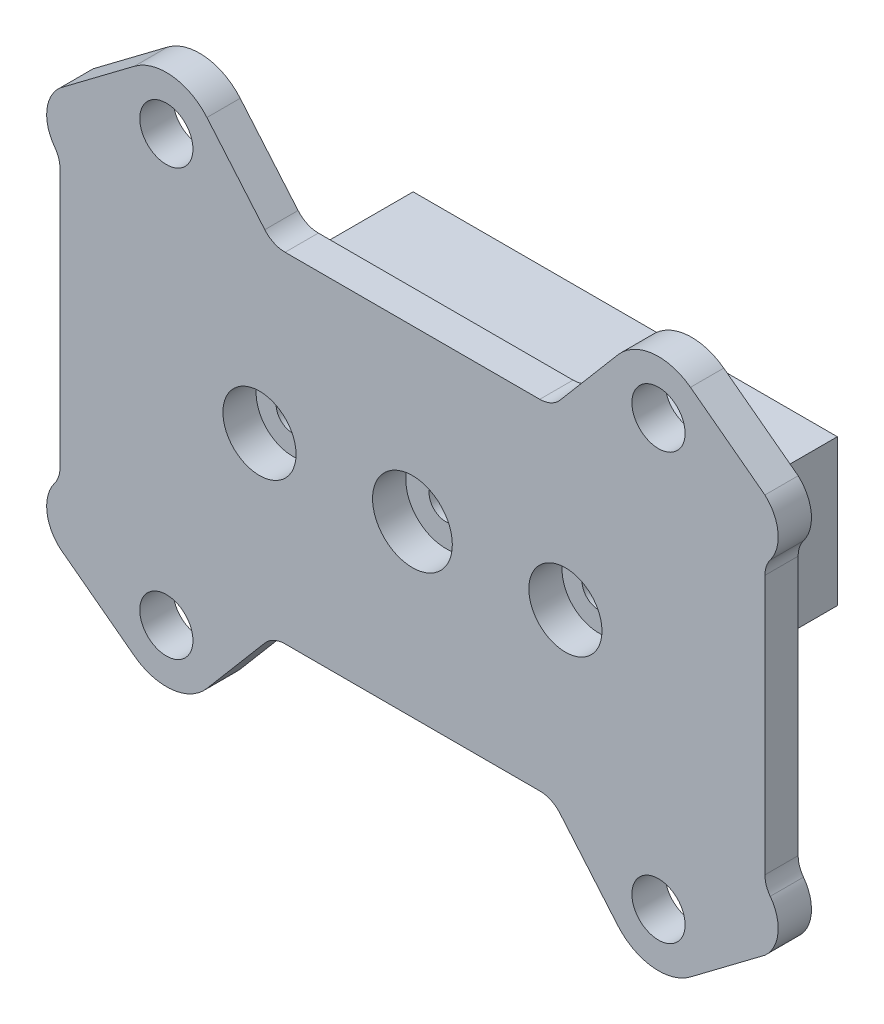
SolidWorks part; units mm, degrees
ref_plane "Front Plane" through (0, 0, 0) normal (0, 0, 1) x (1, 0, 0)
ref_plane "Top Plane" through (0, 0, 0) normal (0, 1, 0) x (1, 0, 0)
ref_plane "Right Plane" through (0, 0, 0) normal (1, 0, 0) x (0, 0, -1)
sketch "Sketch1" plane through (0, 0, 0) normal (0, 0, 1) x (1, 0, 0)
  line L1 (-81.5961, 0) -> (-136.5961, 0) construction
  line L2 (-81.5961, 0) -> (-81.5961, 25.2) construction
  line L3 (-81.5961, 25.2) -> (-136.5961, 25.2) construction
  line L4 (-136.5961, 0) -> (-136.5961, 25.2) construction
  line L5 (-81.5961, 0) -> (-136.5961, 25.2) construction
  line L6 (-81.5961, 25.2) -> (-136.5961, 0) construction
  line L7 (-132.4711, 25.2) -> (-166.0961, 25.2) construction
  line L8 (-146.2488, 0) -> (-142.7398, 0) construction
  line L20 (-97.997, -1.6566) -> (-93.647, -6.7869)
  line L21 (-118.6698, -0.95) -> (-99.5225, -0.95)
  line L22 (-124.5452, -6.7869) -> (-120.1952, -1.6566)
  line L23 (-135.5961, -3.1861) -> (-130.0012, -7.3962)
  line L24 (-135.5961, 21.55) -> (-135.5961, 2.05)
  line L25 (-130.0012, 30.9962) -> (-135.5961, 26.7861)
  line L26 (-120.1952, 25.2566) -> (-124.5452, 30.3869)
  line L27 (-99.5225, 24.55) -> (-118.6698, 24.55)
  line L28 (-93.647, 30.3869) -> (-97.997, 25.2566)
  line L29 (-82.5961, 26.7861) -> (-88.191, 30.9962)
  line L30 (-82.5961, 2.05) -> (-82.5961, 21.55)
  line L31 (-88.191, -7.3962) -> (-82.5961, -3.1861)
  line L32 (-97.997, -1.6566) -> (-93.647, -6.7869)
  line L33 (-118.6698, -0.95) -> (-99.5225, -0.95)
  line L34 (-124.5452, -6.7869) -> (-120.1952, -1.6566)
  line L35 (-135.5961, -3.1861) -> (-130.0012, -7.3962)
  line L36 (-135.5961, 21.55) -> (-135.5961, 2.05)
  line L37 (-130.0012, 30.9962) -> (-135.5961, 26.7861)
  line L38 (-120.1952, 25.2566) -> (-124.5452, 30.3869)
  line L39 (-99.5225, 24.55) -> (-118.6698, 24.55)
  line L40 (-93.647, 30.3869) -> (-97.997, 25.2566)
  line L41 (-82.5961, 26.7861) -> (-88.191, 30.9962)
  line L42 (-82.5961, 2.05) -> (-82.5961, 21.55)
  line L43 (-88.191, -7.3962) -> (-82.5961, -3.1861)
  arc A0 (-82.5961, -3.1861) -> (-82.1961, 0.85) centre (-84.5961, -0.95) ccw construction
  arc A1 (-135.9961, 0.85) -> (-135.5961, -3.1861) centre (-133.5961, -0.95) ccw construction
  arc A18 (-93.647, -6.7869) -> (-88.191, -7.3962) centre (-90.5961, -4.2) ccw
  arc A19 (-97.997, -1.6566) -> (-99.5225, -0.95) centre (-99.5225, -2.95) ccw
  arc A20 (-118.6698, -0.95) -> (-120.1952, -1.6566) centre (-118.6698, -2.95) ccw
  arc A21 (-130.0012, -7.3962) -> (-124.5452, -6.7869) centre (-127.5961, -4.2) ccw
  arc A22 (-135.9961, 0.85) -> (-135.5961, -3.1861) centre (-133.5961, -0.95) ccw
  arc A23 (-135.9961, 0.85) -> (-135.5961, 2.05) centre (-137.5961, 2.05) ccw
  arc A24 (-135.5961, 21.55) -> (-135.9961, 22.75) centre (-137.5961, 21.55) ccw
  arc A25 (-135.5961, 26.7861) -> (-135.9961, 22.75) centre (-133.5961, 24.55) ccw
  arc A26 (-124.5452, 30.3869) -> (-130.0012, 30.9962) centre (-127.5961, 27.8) ccw
  arc A27 (-120.1952, 25.2566) -> (-118.6698, 24.55) centre (-118.6698, 26.55) ccw
  arc A28 (-99.5225, 24.55) -> (-97.997, 25.2566) centre (-99.5225, 26.55) ccw
  arc A29 (-88.191, 30.9962) -> (-93.647, 30.3869) centre (-90.5961, 27.8) ccw
  arc A30 (-82.1961, 22.75) -> (-82.5961, 26.7861) centre (-84.5961, 24.55) ccw
  arc A31 (-82.1961, 22.75) -> (-82.5961, 21.55) centre (-80.5961, 21.55) ccw
  arc A32 (-82.5961, 2.05) -> (-82.1961, 0.85) centre (-80.5961, 2.05) ccw
  arc A33 (-82.5961, -3.1861) -> (-82.1961, 0.85) centre (-84.5961, -0.95) ccw
  arc A34 (-93.647, -6.7869) -> (-88.191, -7.3962) centre (-90.5961, -4.2) ccw
  arc A35 (-97.997, -1.6566) -> (-99.5225, -0.95) centre (-99.5225, -2.95) ccw
  arc A36 (-118.6698, -0.95) -> (-120.1952, -1.6566) centre (-118.6698, -2.95) ccw
  arc A37 (-130.0012, -7.3962) -> (-124.5452, -6.7869) centre (-127.5961, -4.2) ccw
  arc A38 (-135.9961, 0.85) -> (-135.5961, -3.1861) centre (-133.5961, -0.95) ccw
  arc A39 (-135.9961, 0.85) -> (-135.5961, 2.05) centre (-137.5961, 2.05) ccw
  arc A40 (-135.5961, 21.55) -> (-135.9961, 22.75) centre (-137.5961, 21.55) ccw
  arc A41 (-135.5961, 26.7861) -> (-135.9961, 22.75) centre (-133.5961, 24.55) ccw
  arc A42 (-124.5452, 30.3869) -> (-130.0012, 30.9962) centre (-127.5961, 27.8) ccw
  arc A43 (-120.1952, 25.2566) -> (-118.6698, 24.55) centre (-118.6698, 26.55) ccw
  arc A44 (-99.5225, 24.55) -> (-97.997, 25.2566) centre (-99.5225, 26.55) ccw
  arc A45 (-88.191, 30.9962) -> (-93.647, 30.3869) centre (-90.5961, 27.8) ccw
  arc A46 (-82.1961, 22.75) -> (-82.5961, 26.7861) centre (-84.5961, 24.55) ccw
  arc A47 (-82.1961, 22.75) -> (-82.5961, 21.55) centre (-80.5961, 21.55) ccw
  arc A48 (-82.5961, 2.05) -> (-82.1961, 0.85) centre (-80.5961, 2.05) ccw
  arc A49 (-82.5961, -3.1861) -> (-82.1961, 0.85) centre (-84.5961, -0.95) ccw
  ellipse E0 centre (-90.5961, 27.8) end of major axis (-88.8431, 26.8372) minor radius 2 construction
  ellipse E1 centre (-127.5961, 27.8) end of major axis (-128.5589, 26.047) minor radius 2 construction
  ellipse E2 centre (-127.5961, -4.2) end of major axis (-128.5589, -5.953) minor radius 2 construction
  ellipse E3 centre (-90.5961, -4.2) end of major axis (-88.8431, -5.1628) minor radius 2 construction
  ellipse E4 centre (-90.5961, 27.8) end of major axis (-88.8431, 26.8372) minor radius 2
  ellipse E5 centre (-127.5961, 27.8) end of major axis (-128.5589, 26.047) minor radius 2
  ellipse E6 centre (-127.5961, -4.2) end of major axis (-128.5589, -5.953) minor radius 2
  ellipse E7 centre (-90.5961, -4.2) end of major axis (-88.8431, -5.1628) minor radius 2
  point P4 (-109.0961, 12.6)
  dimension "D1" = 0
extrude "Boss-Extrude1" add sketch "Sketch1" along normal blind 2.5
sketch "Sketch2" plane through (0, 0, 0) normal (0, -1, 0) x (1, 0, 0)
  line L0 (-93.7505, -20) -> (-109.0961, -13.6868)
  line L1 (-81.7505, -20) -> (-93.7505, -20) construction
  line L2 (-81.7505, -20) -> (-81.7505, 2.5) construction
  line L3 (-81.7505, 2.5) -> (-86.919, 2.5) construction
  line L4 (-136.4417, -20) -> (-136.4417, 2.5) construction
  line L5 (-81.7505, -20) -> (-136.4417, 2.5) construction
  line L6 (-81.7505, 2.5) -> (-136.4417, -20) construction
  line L7 (-124.4417, -20) -> (-109.0961, -13.6868)
  line L8 (-109.0961, -13.6868) -> (-109.0961, -10.1944) construction
  line L9 (-86.1037, -20) -> (-86.1037, -17.0957) construction
  line L10 (-86.1037, -17.0957) -> (-83.1994, -17.0957) construction
  line L11 (-83.1994, -20) -> (-83.1994, -8.75) construction
  line L12 (-83.1994, -8.75) -> (-81.7505, 2.5) construction
  line L13 (-83.1994, -20) -> (-81.7505, 2.5) construction
  line L14 (-109.0961, -10.1944) -> (-109.0961, 2.5) construction
  line L15 (-134.9928, -20) -> (-136.4417, 2.5) construction
  line L16 (-83.1994, -20) -> (-93.7505, -20) construction
  line L17 (-124.4417, -20) -> (-136.4417, -20) construction
  line L18 (-124.4417, -20) -> (-134.9928, -20) construction
  line L19 (-130.0012, 1.25) -> (-124.5452, 1.25) construction
  line L21 (-131.2732, 2.5) -> (-131.2732, -4)
  line L22 (-131.2732, -4) -> (-123.2732, -4) construction
  line L23 (-123.2732, 2.5) -> (-123.2732, -4)
  line L24 (-131.2732, 2.5) -> (-123.2732, -4) construction
  line L25 (-131.2732, -4) -> (-123.2732, 2.5) construction
  line L26 (-130.0012, 2.5) -> (-130.0012, 0) construction
  line L27 (-124.5452, 2.5) -> (-124.5452, 0) construction
  line L28 (-135.5961, 0) -> (-130.0012, 0) construction
  line L29 (-131.2732, 2.5) -> (-136.4417, 2.5) construction
  line L30 (-94.919, 2.5) -> (-94.919, -4)
  line L31 (-86.919, 2.5) -> (-86.919, -4)
  line L32 (-94.919, 2.5) -> (-123.2732, 2.5)
  line L35 (-124.4417, -20) -> (-134.9928, -20)
  line L36 (-134.9928, -20) -> (-134.9928, 2.5)
  line L37 (-134.9928, 2.5) -> (-131.2732, 2.5)
  line L38 (-93.7505, -20) -> (-83.1994, -20)
  line L39 (-83.1994, -20) -> (-83.1994, 2.5)
  line L40 (-83.1994, 2.5) -> (-86.919, 2.5)
  circle A0 centre (-86.1037, -17.0957) radius 1.0378 construction
  circle A1 centre (-132.0885, -17.0957) radius 1.0378 construction
  circle A2 centre (-109.0961, -10.1944) radius 1.55 construction
  circle A3 centre (-86.1037, -17.0957) radius 1.0378
  circle A4 centre (-132.0885, -17.0957) radius 1.0378
  circle A5 centre (-109.0961, -10.1944) radius 1.55
  arc A6 (-131.2732, -4) -> (-123.2732, -4) centre (-127.2732, -4) ccw
  arc A7 (-86.919, -4) -> (-94.919, -4) centre (-90.919, -4) cw
  point P13 (-109.0961, -8.75)
  point P30 (-127.2732, -0.75)
  point P36 (-127.2732, 1.25)
  point P40 (-127.2732, -4)
  dimension "D1" = 22.5
  dimension "D2" = 12
  dimension "D3" = 8
  dimension "D4" = 4
extrude "Boss-Extrude2" [suppressed] add sketch "Sketch2" along normal blind 2.5
ref_plane "Plane1" [suppressed] through (0, 26.2, 0) normal (0, 1, 0) x (1, 0, 0)
sketch "Sketch3" [suppressed] plane through (-134.9928, 0, 0) normal (-1, 0, 0) x (0, 0, 1)
  line L4 (-20, -2.5) -> (0, -2.5)
  line L5 (0, -2.5) -> (0, 0)
  line L6 (0, 0) -> (-20, 0)
  line L7 (-20, 0) -> (-20, -2.5)
  line L8 (-20, -2.5) -> (0, -2.5)
  line L9 (0, -2.5) -> (0, 0)
  line L10 (0, 0) -> (-20, 0)
  line L11 (-20, 0) -> (-20, -2.5)
  dimension "D1" = 0
extrude "Boss-Extrude3" [suppressed] add sketch "Sketch3" along normal up to surface (1.4489 mm away)
sketch "Sketch4" [suppressed] plane through (-83.1994, 0, 0) normal (1, 0, 0) x (0, 0, -1)
  line L4 (20, 0) -> (0, 0)
  line L5 (0, 0) -> (0, -2.5)
  line L6 (0, -2.5) -> (20, -2.5)
  line L7 (20, -2.5) -> (20, 0)
  line L8 (20, 0) -> (0, 0)
  line L9 (0, 0) -> (0, -2.5)
  line L10 (0, -2.5) -> (20, -2.5)
  line L11 (20, -2.5) -> (20, 0)
  dimension "D1" = 0
extrude "Boss-Extrude4" [suppressed] add sketch "Sketch4" along normal up to surface (1.1719 mm away)
sketch "Sketch5" [suppressed] plane through (0, 26.2, 0) normal (0, 1, 0) x (1, 0, 0)
  line L0 (-120.1952, -2.5) -> (-124.5452, -2.5) construction
  line L1 (-120.9952, -2.5) -> (-97.1971, -2.5)
  line L2 (-120.9952, -2.5) -> (-120.9952, 7.5)
  line L3 (-120.9952, 7.5) -> (-97.1971, 7.5)
  line L4 (-97.1971, -2.5) -> (-97.1971, 7.5)
  line L5 (-120.9952, -2.5) -> (-97.1971, 7.5) construction
  line L6 (-120.9952, 7.5) -> (-97.1971, -2.5) construction
  line L11 (-132.0885, 17.0957) -> (-86.1037, 17.0957) construction
  point P4 (-109.0961, 2.5)
  point P7 (-109.0961, 17.0957)
  dimension "D1" = 10
extrude "Boss-Extrude5" [suppressed] add sketch "Sketch5" along normal blind 2
sketch "Sketch6" [suppressed] plane through (0, 26.2, 0) normal (0, -1, 0) x (1, 0, 0)
  line L0 (-93.647, 2.5) -> (-97.997, 2.5) construction
  line L1 (-123.2732, 0) -> (-97.1971, 0)
  line L2 (-123.2732, 0) -> (-123.2732, 2.5)
  line L3 (-123.2732, 2.5) -> (-97.1971, 2.5)
  line L4 (-97.1971, 0) -> (-97.1971, 2.5)
  line L5 (-123.2732, 0) -> (-97.1971, 2.5) construction
  line L6 (-123.2732, 2.5) -> (-97.1971, 0) construction
  line L7 (-97.1971, 2.5) -> (-97.1971, -7.5) construction
  point P4 (-110.2351, 1.25)
extrude "Boss-Extrude6" [suppressed] add sketch "Sketch6" along normal up to surface (1.65 mm away)
sketch "Sketch7" [suppressed] plane through (-120.9952, 0, 0) normal (-1, 0, 0) x (0, 0, 1)
  line L4 (-7.5, 26.2) -> (2.5, 26.2)
  line L5 (2.5, 26.2) -> (2.5, 28.2)
  line L6 (2.5, 28.2) -> (-7.5, 28.2)
  line L7 (-7.5, 28.2) -> (-7.5, 26.2)
  line L8 (-7.5, 26.2) -> (2.5, 26.2)
  line L9 (2.5, 26.2) -> (2.5, 28.2)
  line L10 (2.5, 28.2) -> (-7.5, 28.2)
  line L11 (-7.5, 28.2) -> (-7.5, 26.2)
  dimension "D1" = 0
extrude "Boss-Extrude7" [suppressed] add sketch "Sketch7" along normal up to surface (1.6958 mm away)
sketch "Sketch8" [suppressed] plane through (-97.1971, 0, 0) normal (1, 0, 0) x (0, 0, -1)
  line L5 (-2.5, 26.2) -> (0, 26.2)
  line L6 (0, 26.2) -> (7.5, 26.2)
  line L7 (7.5, 26.2) -> (7.5, 28.2)
  line L8 (7.5, 28.2) -> (-2.5, 28.2)
  line L9 (-2.5, 28.2) -> (-2.5, 26.2)
  line L10 (-2.5, 26.2) -> (0, 26.2)
  line L11 (0, 26.2) -> (7.5, 26.2)
  line L12 (7.5, 26.2) -> (7.5, 28.2)
  line L13 (7.5, 28.2) -> (-2.5, 28.2)
  line L14 (-2.5, 28.2) -> (-2.5, 26.2)
  dimension "D1" = 0
extrude "Boss-Extrude8" [suppressed] add sketch "Sketch8" along normal up to surface (1.6958 mm away)
other "Move Face2" [suppressed] offset 1 parameters "D1"=1
fillet "Fillet2" [suppressed] type full round
fillet "Fillet3" [suppressed] type full round
fillet "Fillet7" [suppressed] radius 1.25
fillet "Fillet4" [suppressed] radius 1.25
fillet "Fillet5" [suppressed] type full round
other "Move Face3" [suppressed] offset 0.325 parameters "D1"=0.325
other "Move Face4" [suppressed] flip direction yes offset 0.185 parameters "D1"=0.185
other "Move Face5" [suppressed] flip direction yes offset 0.185 parameters "D1"=0.185
sketch "Sketch10" [suppressed] plane through (0, 28.2, 0) normal (0, 1, 0) x (1, 0, 0)
  line L0 (-122.691, 7.5) -> (-110.442, 13.1252)
  line L1 (-95.5013, 7.5) -> (-107.7502, 13.1252)
  line L2 (-122.691, 7.5) -> (-95.5013, 7.5)
  circle A0 centre (-109.0961, 10.1944) radius 1.225 construction
  circle A1 centre (-109.0961, 10.1944) radius 1.225
  arc A2 (-107.7502, 13.1252) -> (-110.442, 13.1252) centre (-109.0961, 10.1944) ccw
  circle A3 centre (-109.0961, 10.1944) radius 3.225 construction
  dimension "D1" = 2
other "Move Face6" [suppressed] offset 7 parameters "D1"=7
sketch "Sketch11" [suppressed] plane through (0, 28.2, 0) normal (0, 1, 0) x (1, 0, 0)
  line L0 (-122.691, 7.5) -> (-129.9246, 24.9895)
  line L1 (-129.9246, 24.9895) -> (-92.82, 26.2967)
  line L2 (-92.82, 26.2967) -> (-95.5013, 7.5)
  line L3 (-110.442, 13.1252) -> (-122.691, 7.5)
  line L4 (-95.5013, 7.5) -> (-107.7502, 13.1252)
  line L5 (-122.691, 7.5) -> (-95.5013, 7.5)
  line L6 (-110.442, 13.1252) -> (-122.691, 7.5)
  line L7 (-95.5013, 7.5) -> (-107.7502, 13.1252)
  line L8 (-122.691, 7.5) -> (-95.5013, 7.5)
  circle A1 centre (-109.0961, 10.1944) radius 1.225
  circle A2 centre (-109.0961, 10.1944) radius 1.225
  arc A3 (-107.7502, 13.1252) -> (-110.442, 13.1252) centre (-109.0961, 10.1944) ccw
  arc A4 (-107.7502, 13.1252) -> (-110.442, 13.1252) centre (-109.0961, 10.1944) ccw
  line M6 (-95.5013, 14.5) -> (-122.691, 14.5)
  line M7 (-122.691, 14.5) -> (-122.691, 0)
  line M11 (-95.5013, 0) -> (-95.5013, 14.5)
  dimension "D1" = 0
  dimension "D2" = 0
extrude "Cut-Extrude1" [suppressed] cut sketch "Sketch11" against normal blind 10 contours L2 L1 L0 M7 M6 M11 | A4 L7 L6 M11 M6 M7 | A2
fillet "Fillet6" [suppressed] radius 1.5
ref_plane "Plane2" through (0, 11.8, 0) normal (0, 1, 0) x (1, 0, 0)
ref_plane "Plane3" through (-109.0961, 0, 0) normal (-1, 0, 0) x (0, 0, 1)
other "Move Face7" [suppressed] offset 3 parameters "D1"=3
sketch "Sketch14" plane through (0, 0, 0) normal (0, 0, -1) x (-1, 0, 0)
  line L1 (135.5961, 2.05) -> (82.5961, 2.05) construction
  line L2 (135.5961, 2.05) -> (135.5961, 21.55) construction
  line L3 (135.5961, 21.55) -> (82.5961, 21.55) construction
  line L4 (82.5961, 2.05) -> (82.5961, 21.55) construction
  line L5 (135.5961, 2.05) -> (82.5961, 21.55) construction
  line L6 (135.5961, 21.55) -> (82.5961, 2.05) construction
  line L7 (125.0419, 17.3) -> (93.1504, 17.3)
  line L8 (125.0419, 17.3) -> (125.0419, 6.3)
  line L9 (125.0419, 6.3) -> (93.1504, 6.3)
  line L10 (93.1504, 17.3) -> (93.1504, 6.3)
  line L11 (125.0419, 17.3) -> (93.1504, 6.3) construction
  line L12 (125.0419, 6.3) -> (93.1504, 17.3) construction
  point P4 (109.0961, 11.8)
  point P7 (109.0961, 11.8)
extrude "Boss-Extrude9" add sketch "Sketch14" along normal up to surface (13.5 mm away)
sketch "Sketch12" plane through (0, 0, 2.5) normal (0, 0, 1) x (1, 0, 0)
  line L0 (-135.5961, 11.8) -> (-82.5961, 11.8) construction
  line L1 (-135.5961, 21.55) -> (-135.5961, 2.05) construction
  line L2 (-82.5961, 2.05) -> (-82.5961, 21.55) construction
  line L3 (-120.5961, 11.8) -> (-97.5961, 11.8) construction
  circle A0 centre (-97.5961, 11.8) radius 1.25
  circle A1 centre (-120.5961, 11.8) radius 1.25
  circle A2 centre (-109.0961, 11.8) radius 1.25
  point P9 (-109.0961, 11.8)
  dimension "D1" = 2.5
  dimension "D3" = 2.5
  dimension "D2" = 23
extrude "Cut-Extrude2" cut sketch "Sketch12" against normal through all both and the other way through all
fillet "Fillet9" radius 6 4 edges at (-109.0961, 6.3, 0) (-125.0419, 11.8, 0) (-93.1504, 11.8, 0) (-109.0961, 17.3, 0)
sketch "Sketch15" plane through (0, 0, 2.5) normal (0, 0, 1) x (1, 0, 0)
  circle A0 centre (-120.5961, 11.8) radius 2.75
  circle A1 centre (-109.0961, 11.8) radius 3
  circle A2 centre (-97.5961, 11.8) radius 2.75
  dimension "D1" = 5.5
  dimension "D2" = 6
extrude "Cut-Extrude3" cut sketch "Sketch15" against normal blind 2.5
fillet "Fillet10" [suppressed] radius 2
